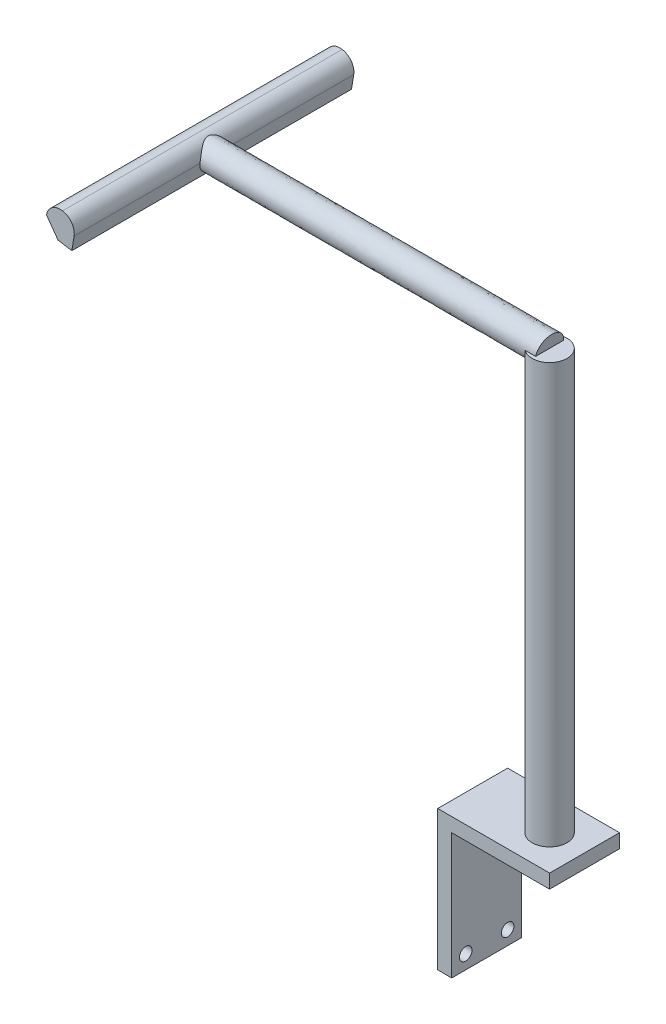
SolidWorks part; units mm, degrees
ref_plane "Płaszczyzna przednia" through (0, 0, 0) normal (0, 0, 1) x (1, 0, 0)
ref_plane "Płaszczyzna górna" through (0, 0, 0) normal (0, 1, 0) x (1, 0, 0)
ref_plane "Płaszczyzna prawa" through (0, 0, 0) normal (1, 0, 0) x (0, 0, -1)
sketch "Szkic1" plane through (0, 0, 0) normal (1, 0, 0) x (0, 0, -1)
  line L1 (0, 0) -> (50, 0)
  line L2 (0, 0) -> (0, 100)
  line L3 (0, 100) -> (50, 100)
  line L4 (50, 0) -> (50, 100)
  circle A0 centre (10, 10) radius 4.5
  circle A1 centre (40, 10) radius 4.5
  dimension "D1" = 9
  dimension "D2" = 9
  dimension "D3" = 50
  dimension "D4" = 100
  dimension "D5" = 10
  dimension "D6" = 10
  dimension "D7" = 10
  dimension "D8" = 10
extrude "Dodanie-wyciągnięcie1" add sketch "Szkic1" along normal blind 10
sketch "Szkic2" plane through (0, 0, -50) normal (0, 0, -1) x (-1, 0, 0)
  line L1 (0, 100) -> (-80, 100)
  line L2 (0, 100) -> (0, 90)
  line L3 (0, 90) -> (-80, 90)
  line L4 (-80, 100) -> (-80, 90)
  dimension "D1" = 10
  dimension "D2" = 80
extrude "Dodanie-wyciągnięcie2" add sketch "Szkic2" against normal blind 50
sketch "Szkic3" plane through (0, 100, 0) normal (0, 1, 0) x (1, 0, 0)
  line L0 (80, 0) -> (80, 50) construction
  line L1 (80, 0) -> (0, 0) construction
  circle A0 centre (55, 25) radius 12.5
  dimension "D1" = 25
  dimension "D2" = 25
  dimension "D3" = 25
extrude "Dodanie-wyciągnięcie3" add sketch "Szkic3" along normal blind 300
sketch "Szkic4" plane through (0, 400, 0) normal (0, 1, 0) x (1, 0, 0)
  line L0 (55, 25) -> (-185, 25)
  point P2 (-157.5389, 25)
  point P3 (-145.6789, 25)
  dimension "D1" = 240
ref_plane "Płaszczyzna1" through (-243.5394, 39.5527, 0) normal (-0.9871, 0.1603, 0) x (0, 0, 1)
sketch "Szkic6" plane through (-243.5394, 39.5527, 0) normal (-0.9871, 0.1603, 0) x (0, 0, 1)
  line L0 (-25, 403.6438) -> (-25, 365.17) construction
  circle A0 centre (-25, 364.6685) radius 10
  dimension "D1" = 20
sweep "Wyciągnięcie po ścieżce1" add profiles "Szkic6" path "Szkic4"
sketch "Szkic7" plane through (-243.5394, 39.5527, 0) normal (-0.9871, 0.1603, 0) x (0, 0, 1)
  line L1 (-125, 354.6685) -> (75, 354.6685)
  line L2 (-125, 354.6685) -> (-125, 374.6685)
  line L3 (-125, 374.6685) -> (75, 374.6685)
  line L4 (75, 354.6685) -> (75, 374.6685)
  line L5 (-125, 354.6685) -> (75, 374.6685) construction
  line L6 (-125, 374.6685) -> (75, 354.6685) construction
  point P0 (-25, 364.6685)
  dimension "D1" = 20
  dimension "D2" = 200
extrude "Dodanie-wyciągnięcie4" add sketch "Szkic7" along normal blind 20
fillet "Zaokrąglenie1" radius 10 2 edges at (-183.4773, 409.3756, 25) (-203.2187, 412.5818, -25)
chamfer "Sfazowanie1" distance 10 angle 45 1 edges at (-206.4248, 392.8404, -25)
